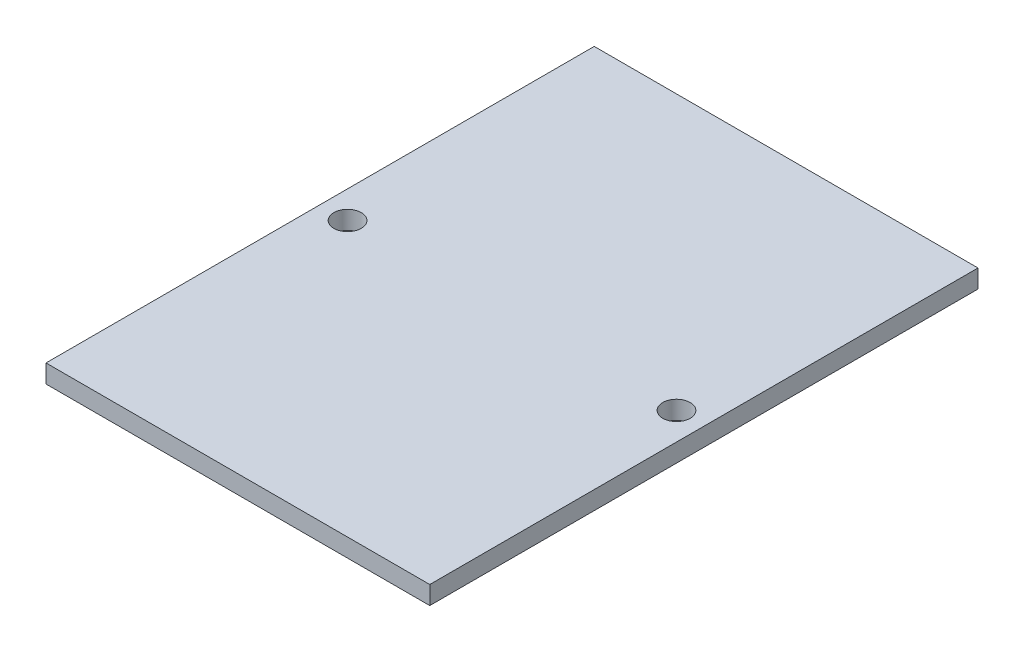
SolidWorks part; units mm, degrees
ref_plane "前视基准面" through (0, 0, 0) normal (0, 0, 1) x (1, 0, 0)
ref_plane "上视基准面" through (0, 0, 0) normal (0, 1, 0) x (1, 0, 0)
ref_plane "右视基准面" through (0, 0, 0) normal (1, 0, 0) x (0, 0, -1)
sketch "Sketch1" plane through (0, 0, 0) normal (0, 1, 0) x (1, 0, 0)
  line L1 (-21, 30) -> (21, 30)
  line L2 (-21, 30) -> (-21, -30)
  line L3 (-21, -30) -> (21, -30)
  line L4 (21, 30) -> (21, -30)
  line L5 (-21, 30) -> (21, -30) construction
  line L6 (-21, -30) -> (21, 30) construction
  circle A0 centre (18, 0) radius 1.5
  circle A1 centre (-18, 0) radius 1.5
  point P0 (0, 0)
  dimension "D3" = 3
  dimension "D4" = 3
  dimension "D5" = 18
  dimension "D6" = 18
  dimension "D1" = 42
  dimension "D2" = 60
extrude "Boss-Extrude1" add sketch "Sketch1" along normal blind 2
